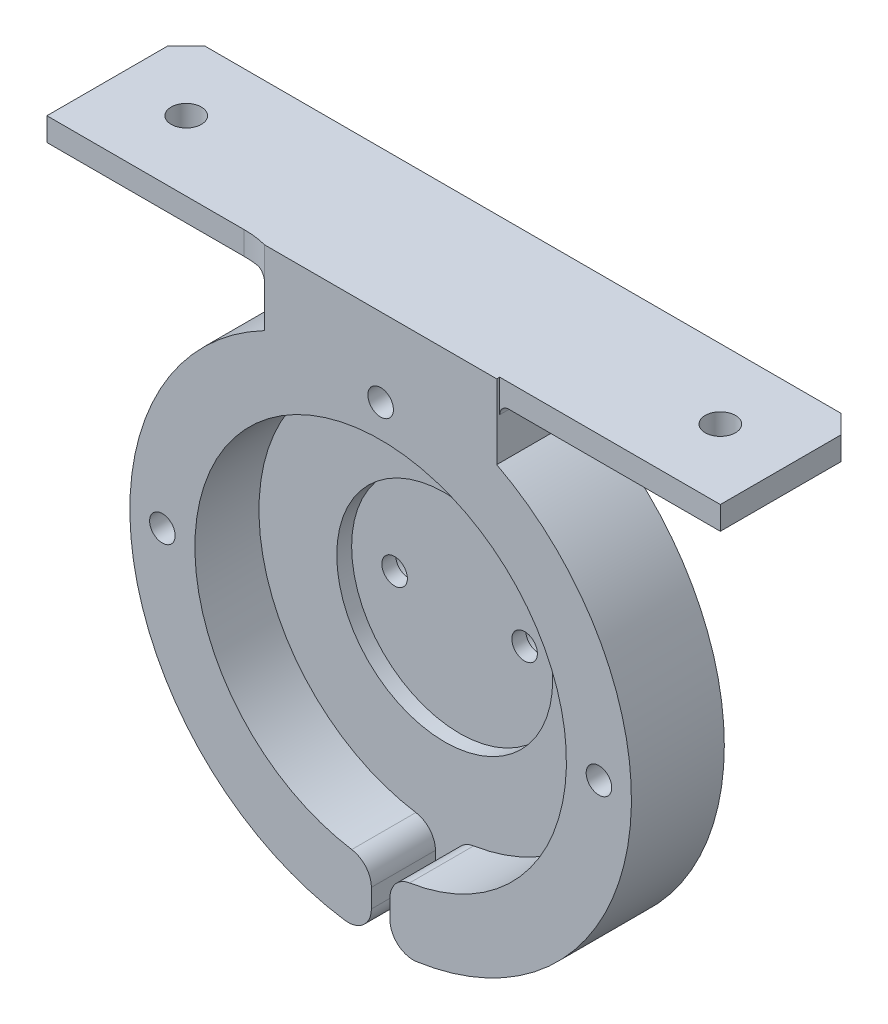
SolidWorks part; units mm, degrees
ref_plane "Front Plane" through (0, 0, 0) normal (0, 0, 1) x (1, 0, 0)
ref_plane "Top Plane" through (0, 0, 0) normal (0, 1, 0) x (1, 0, 0)
ref_plane "Right Plane" through (0, 0, 0) normal (1, 0, 0) x (0, 0, -1)
sketch "Sketch1" plane through (0, 0, 0) normal (0, 0, 1) x (1, 0, 0)
  circle A0 centre (0, 0) radius 27
  circle A1 centre (0, 0) radius 23.5 construction
  circle A2 centre (0, 23.5) radius 1.375
  circle A3 centre (23.5, 0) radius 1.375
  circle A4 centre (0, -23.5) radius 1.375 construction
  circle A5 centre (-23.5, 0) radius 1.375
  circle A6 centre (0, 0) radius 20
  point P15 (0, 0)
  dimension "D1" = 54
  dimension "D2" = 47
  dimension "D3" = 2.75
  dimension "D5" = 40
  dimension "D4" = 4
extrude "Boss-Extrude1" add sketch "Sketch1" along normal blind 10
sketch "Sketch3" plane through (0, 0, 0) normal (0, 0, 1) x (1, 0, 0)
  circle A0 centre (0, 0) radius 20
  circle A1 centre (0, 0) radius 7 construction
  circle A2 centre (-7, 0) radius 1.375
  circle A3 centre (7, 0) radius 1.375
  circle A4 centre (0, 0) radius 11.5 construction
  dimension "D1" = 40
  dimension "D2" = 14
  dimension "D3" = 2.75
  dimension "D4" = 23
extrude "Boss-Extrude2" add sketch "Sketch3" along normal blind 1.5
sketch "Sketch5" plane through (0, 0, 10) normal (0, 0, 1) x (1, 0, 0)
  line L0 (0, -5.5) -> (0, 5.5) construction
  line L1 (-12.5, 23.9322) -> (-4.2519, 23.9322)
  line L2 (-12.5, 23.9322) -> (-12.5, 31.9322)
  line L3 (-12.5, 31.9322) -> (12.5, 31.9322)
  line L4 (12.5, 23.9322) -> (12.5, 31.9322)
  line L5 (4.2678, 23.9322) -> (0, 26.2545)
  line L6 (0, 26.2545) -> (-4.2519, 23.9322)
  line L7 (4.2678, 23.9322) -> (12.5, 23.9322)
  circle A0 centre (0, 0) radius 27 construction
  dimension "D1" = 12.5
  dimension "D2" = 25
  dimension "D3" = 8
extrude "Boss-Extrude3" add sketch "Sketch5" against normal blind 6
sketch "Sketch6" plane through (0, 31.9322, 0) normal (0, 1, 0) x (1, 0, 0)
  line L0 (12.5, -4) -> (12.5, -10) construction
  line L1 (-12.5, -10) -> (12.5, -10)
  line L2 (-12.5, -10) -> (-12.5, 5.32)
  line L3 (-12.5, 5.32) -> (12.5, 5.32)
  line L4 (12.5, -10) -> (12.5, 5.32)
  dimension "D1" = 15.32
extrude "Boss-Extrude4" add sketch "Sketch6" against normal blind 2.5
sketch "Sketch7" plane through (0, 31.9322, 0) normal (0, 1, 0) x (1, 0, 0)
  line L0 (0, -5.5) -> (0, 5.5) construction
  line L1 (-36.25, -67.18) -> (36.25, -67.18) construction
  line L2 (-36.25, -67.18) -> (-36.25, 1.32) construction
  line L3 (-32.25, 5.32) -> (32.25, 5.32) construction
  line L4 (36.25, -67.18) -> (36.25, 1.32) construction
  line L5 (-28.75, -9.68) -> (-36.25, -9.68)
  line L6 (0, 5.32) -> (-36.25, 5.32)
  line L7 (-36.25, -9.68) -> (-36.25, -2.18)
  line L8 (12.5, -4) -> (-12.5, -4) construction
  line L9 (0, 5.32) -> (0, -9.68)
  line L10 (0, -9.68) -> (-28.75, -9.68)
  line L11 (-36.25, 5.32) -> (-36.25, -2.18)
  arc A0 (32.25, 5.32) -> (36.25, 1.32) centre (32.25, 1.32) cw construction
  circle A3 centre (-28.75, -2.18) radius 1.625
  point P4 (0, 5.32)
  point P11 (36.25, 5.32)
  point P14 (-36.25, 5.32)
  point P21 (-36.25, -9.68)
  dimension "D4" = 4
  dimension "D7" = 3.25
  dimension "D1" = 72.5
  dimension "D2" = 72.5
  dimension "D3" = 9.32
  dimension "D5" = 15
extrude "Boss-Extrude5" add sketch "Sketch7" against normal blind 2.5 contours L10 L9 L6 L11 A3 region at (-17.9604, 31.9322, 2.18)
fillet "Fillet2" radius 10 1 edges at (-12.5, 30.6822, 9.68)
sketch "Sketch8" plane through (0, 31.9322, 0) normal (0, 1, 0) x (1, 0, 0)
  circle A0 centre (-28.75, -2.18) radius 2.5
  circle A1 centre (-28.75, -2.18) radius 4
  dimension "D1" = 5
  dimension "D2" = 8
extrude "Boss-Extrude6" [suppressed] add sketch "Sketch8" against normal blind 5
mirror "Mirror1" about plane through (0, 0, 0) normal (1, 0, 0) of "Boss-Extrude4", "Boss-Extrude5", "Boss-Extrude6"
fillet "Fillet3" radius 1 3 edges at (0, 29.4322, 4) (12.5, 29.4322, 6.84) (-12.5, 29.4322, 7)
fillet "Fillet4" [suppressed] radius 10
chamfer "Chamfer1" distance 2 angle 45 2 edges at (-36.25, 30.6822, -5.32) (36.25, 30.6822, -5.32)
sketch "Sketch14" plane through (0, 0, 1.5) normal (0, 0, 1) x (1, 0, 0)
  circle A0 centre (0, 0) radius 11.625
  circle A1 centre (0, 0) radius 20
  dimension "D1" = 23.25
extrude "Boss-Extrude10" add sketch "Sketch14" along normal blind 1.6
sketch "Sketch9" plane through (0, 0, 1.5) normal (0, 0, 1) x (1, 0, 0)
  circle A0 centre (0, 0) radius 12
  circle A1 centre (0, 0) radius 20
  dimension "D1" = 24
extrude "Boss-Extrude7" [suppressed] add sketch "Sketch9" along normal up to surface (8.5 mm away) up to face at (-2.5, 17.8458, 10)
sketch "Sketch4" plane through (0, 0, 0) normal (0, 1, 0) x (1, 0, 0)
  line L0 (12.5, -10) -> (-12.5, -10) construction
  line L1 (-1, -3.1) -> (1, -3.1)
  line L2 (-1, -3.1) -> (-1, -10)
  line L3 (-1, -10) -> (1, -10)
  line L4 (1, -3.1) -> (1, -10)
  line L6 (-11.625, -3.1) -> (11.625, -3.1) construction
  point P7 (0, -3.1)
  dimension "D2" = 2
extrude "Cut-Extrude1" cut sketch "Sketch4" against normal up to surface (26.9815 mm away) up to face at (0, 11.9661, 7)
fillet "Fillet6" [suppressed] radius 2
sketch "Sketch10" [suppressed] plane through (0, 0, 10) normal (0, 0, 1) x (1, 0, 0)
  line L0 (-4.25, -19.5432) -> (-4.25, -13.8632)
  line L1 (-1.75, -24.7171) -> (-1.75, -13.4884) construction
  line L2 (0, -8.4586) -> (0, 8.4586) construction
  line L3 (4.25, -19.5432) -> (4.25, -13.8632)
  arc A0 (4.25, -19.5432) -> (-4.25, -19.5432) centre (0, 0) ccw
  arc A1 (-12.5, 23.9322) -> (-4.05, -26.6945) centre (0, 0) ccw construction
  arc A2 (4.25, -13.8632) -> (-4.25, -13.8632) centre (0, 0) ccw
  circle A3 centre (0, 0) radius 12 construction
  dimension "D1" = 7
  dimension "D2" = 2.5
  dimension "D3" = 2.5
extrude "Cut-Extrude2" [suppressed] cut sketch "Sketch10" against normal up to surface (6.5 mm away) up to face at (0, -13.4891, 3.1)
sketch "Sketch12" plane through (0, 0, 0) normal (0, 0, -1) x (-1, 0, 0)
  line L2 (0, 8.4586) -> (0, -8.4586) construction
  line L3 (-3.75, 5.6125) -> (-2.6485, 4.2998)
  line L4 (8.4586, 0) -> (-8.4586, 0) construction
  line L5 (3.75, 5.6125) -> (2.6485, 4.2998)
  arc A0 (2.6485, 4.2998) -> (-2.6485, 4.2998) centre (0, 0) ccw construction
  arc A1 (-2.6485, 4.2998) -> (2.6485, 4.2998) centre (0, 0) cw
  circle A2 centre (0, 0) radius 6.75 construction
  arc A3 (3.75, 5.6125) -> (-3.75, 5.6125) centre (0, 0) ccw
  circle A4 centre (0, 0) radius 5.05 construction
  dimension "D1" = 10.1
  dimension "D2" = 13.5
  dimension "D3" = 3.75
  dimension "D4" = 3.75
  dimension "D5" = 50
  dimension "D6" = 50
extrude "Boss-Extrude8" [suppressed] add sketch "Sketch12" along normal blind 4.5
fillet "Fillet7" [suppressed] radius 1
sketch "Sketch13" plane through (0, 0, 0) normal (0, 0, -1) x (-1, 0, 0)
  circle A0 centre (0, 0) radius 2.5
  dimension "D1" = 5
extrude "Boss-Extrude9" add sketch "Sketch13" along normal blind 5.27
fillet "Fillet9" radius 2.5 4 edges at (1, -26.9815, 6.55) (-1, -26.9815, 6.55) (-1, -19.975, 6.55) (1, -19.975, 6.55)
sketch "Sketch15" plane through (0, 0, 0) normal (0, 0, -1) x (-1, 0, 0)
  circle A0 centre (0, 0) radius 12.5
  dimension "D1" = 25
extrude "Boss-Extrude11" add sketch "Sketch15" along normal blind 2.77
sketch "Sketch16" plane through (0, 0, -2.77) normal (0, 0, -1) x (-1, 0, 0)
  circle A0 centre (7, 0) radius 2.5
  circle A1 centre (-7, 0) radius 2.5
  dimension "D1" = 5
extrude "Cut-Extrude3" cut sketch "Sketch16" against normal up to surface (2.77 mm away) up to face at (12.5, 0, 0)
fillet "Fillet10" radius 1.75 1 edges at (-2.5, 0, -5.27)
